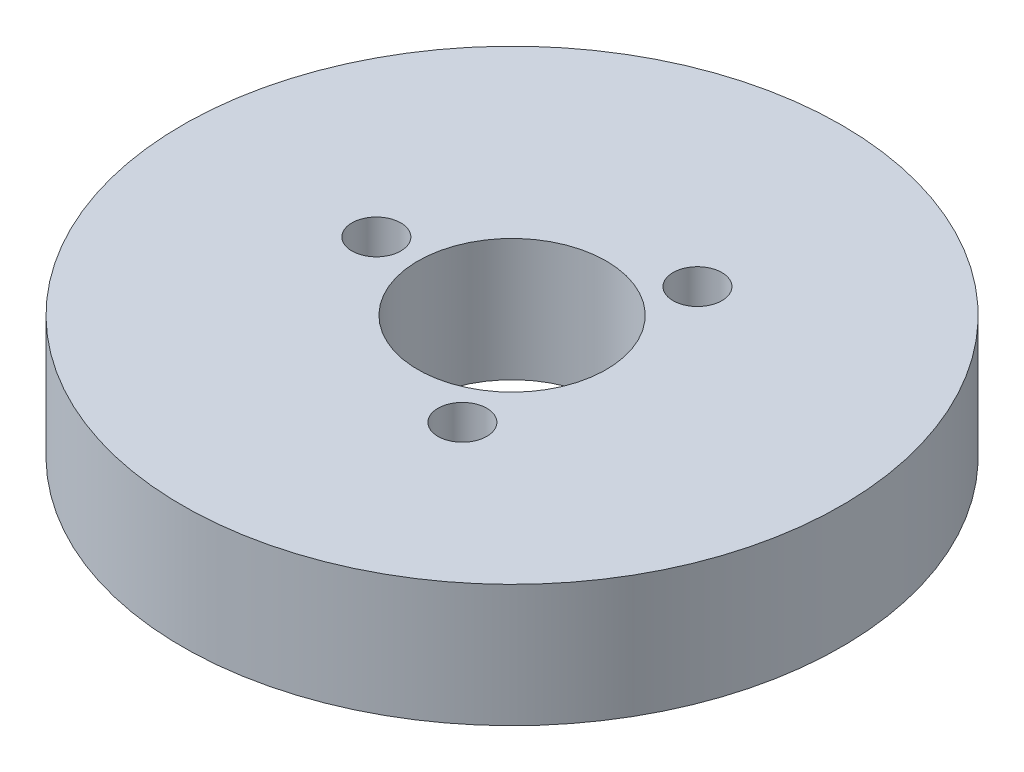
SolidWorks part; units mm, degrees
ref_plane "Front Plane" through (0, 0, 0) normal (0, 0, 1) x (1, 0, 0)
ref_plane "Top Plane" through (0, 0, 0) normal (0, 1, 0) x (1, 0, 0)
ref_plane "Right Plane" through (0, 0, 0) normal (1, 0, 0) x (0, 0, -1)
sketch "Sketch1" plane through (0, 0, 0) normal (0, 1, 0) x (1, 0, 0)
  circle A0 centre (0, 0) radius 70
  dimension "FLANGE_OD" = 140
extrude "Boss-Extrude1" add sketch "Sketch1" along normal blind 26
sketch "Sketch2" plane through (0, 0, 0) normal (0, 1, 0) x (1, 0, 0)
  circle A0 centre (0, 0) radius 20
  dimension "BORE_D" = 40
extrude "Cut-Extrude1" cut sketch "Sketch2" along normal through all
sketch "Sketch3" plane through (0, 26, 0) normal (0, 1, 0) x (1, 0, 0)
  circle A0 centre (0, 0) radius 28.8246 construction
  circle A1 centre (-28.8246, 0) radius 5.1866
  dimension "BOLT_D" = 10.3731
  dimension "BOLT_PCD" = 57.6492
extrude "Cut-Extrude2" cut sketch "Sketch3" against normal blind 21.399
pattern_circular "CirPattern1" count 3 over 360 about axis through (0, 0, 0) along (0, 1, 0) of "Cut-Extrude2"
